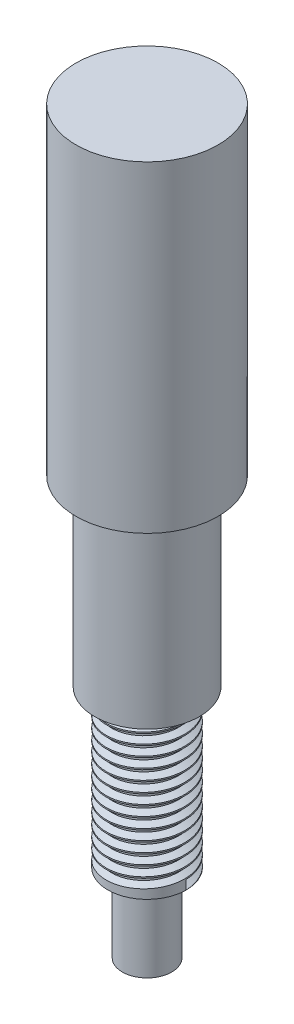
SolidWorks part; units mm, degrees
material "AISI 316 Annealed Stainless Steel Bar (SS)"
ref_plane "Front Plane" through (0, 0, 0) normal (0, 0, 1) x (1, 0, 0)
ref_plane "Top Plane" through (0, 0, 0) normal (0, 1, 0) x (1, 0, 0)
ref_plane "Right Plane" through (0, 0, 0) normal (1, 0, 0) x (0, 0, -1)
sketch "Sketch2" plane through (0, 0, 0) normal (0, 0, 1) x (1, 0, 0)
  line L0 (0, 0) -> (0, 508.8276) construction
  line L1 (0, 0) -> (6, 0)
  line L2 (0, 0) -> (0, 19.05)
  line L3 (0, 19.05) -> (6, 19.05)
  line L4 (6, 0) -> (6, 19.05)
  line L5 (0, 19.05) -> (9.525, 19.05)
  line L6 (0, 19.05) -> (0, 57.15)
  line L7 (0, 57.15) -> (9.525, 57.15)
  line L8 (9.525, 19.05) -> (9.525, 57.15)
  line L9 (0, 57.15) -> (12.721, 57.15)
  line L10 (0, 57.15) -> (0, 101.6)
  line L11 (0, 101.6) -> (12.721, 101.6)
  line L12 (12.721, 57.15) -> (12.721, 101.6)
  line L13 (0, 101.6) -> (17.272, 101.6)
  line L14 (0, 101.6) -> (0, 179.832)
  line L15 (0, 179.832) -> (17.272, 179.832)
  line L16 (17.272, 101.6) -> (17.272, 179.832)
  dimension "D1" = 78.232
  dimension "D2" = 17.272
  dimension "D4" = 44.45
  dimension "D3" = 12.721
  dimension "D5" = 38.1
  dimension "D6" = 9.525
  dimension "D7" = 19.05
  dimension "D8" = 6
revolve "Revolve1" add sketch "Sketch2" angle 360 about L0 region at (3, 9.525, 0) region at (4.7625, 38.1, 0) region at (6.3605, 79.375, 0) region at (8.636, 140.716, 0)
thread "Thread2" pitch 2.54 method cut profile "Thread Profile3" start angle 0, offset 0, length 0, pitch 2.54, diameter 19.05
ref_plane "Plane3" through (9.525, 19.05, 0) normal (0, 0, 1) x (1, 0, 0)
sketch "Thread Profile3" plane through (9.525, 19.05, 0) normal (0, 0, 1) x (1, 0, 0)
  line L0 (0, 0) -> (0, 2.54) construction
  line L11 (0, 0) -> (0, 2.2225)
  line L12 (0, 2.2225) -> (-1.3748, 1.4287)
  line L13 (-1.3748, 1.4287) -> (-1.3748, 0.7937)
  line L15 (-1.3748, 0.7937) -> (0, 0)
  line L17 (-1.3748, 1.1112) -> (0, 1.1112) construction
  point P2 (0, 0)
  dimension "Pitch" = 2.54
  dimension "Profile_Angle" = 60
  dimension "Profile_Land" = 0.635
  dimension "Profile_Height" = 1.3748
equation "\"hole diamiter\"= 1.36in"
equation "\"wheel depth\"= 2.88"
equation "\"press_tolerance\"= 0.00165"
equation "\"wheel_connection\"= \"hole diamiter\"'https://at-machining.com/tolerance-press-fit/"
equation "\"D1@Sketch2\"=\"wheel depth\"+0.2"
equation "\"D2@Sketch2\"=\"wheel_connection\"/2"
equation "\"fitting depth\"=1.75"
equation "\"D4@Sketch2\"=\"fitting depth\""
equation "\"bearing_id\"= 1"
equation "\"bearing_connection\"= \"bearing_id\" + \"press_tolerance\"'https://at-machining.com/tolerance-press-fit/"
equation "\"D3@Sketch2\"=\"bearing_connection\"/2"
equation "\"thread length\" = 1.5"
equation "\"major_diamiter\"= 0.75 'https://www.machiningdoctor.com/threadinfo/?tid=81"
equation "\"D5@Sketch2\"=\"thread length\""
equation "\"D6@Sketch2\"=\"major_diamiter\"/2"
equation "\"coupling diamiter\"= 12mm"
equation "\"coupling lenght\"= 1.5 / 2"
equation "\"D7@Sketch2\"=\"coupling lenght\""
equation "\"D8@Sketch2\"=\"coupling diamiter\"/2"
